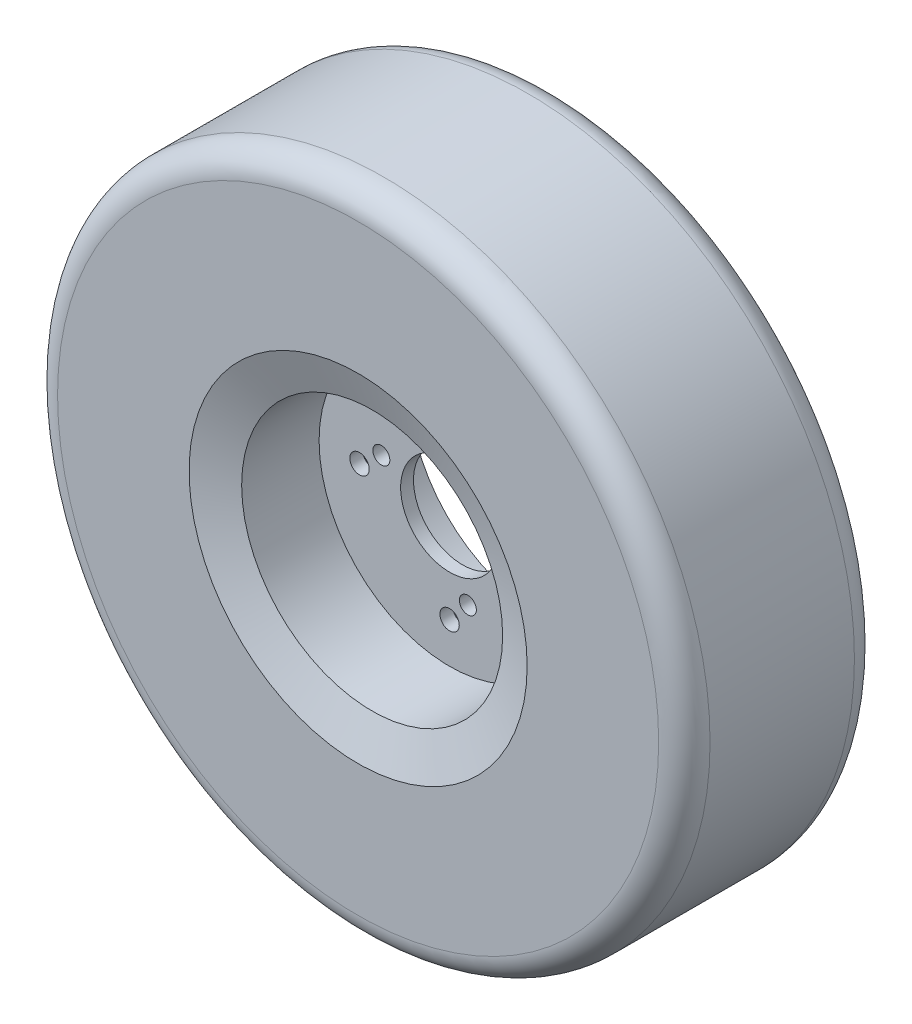
SolidWorks part; units mm, degrees
material "wheel"
ref_plane "Front Plane" through (0, 0, 0) normal (0, 0, 1) x (1, 0, 0)
ref_plane "Top Plane" through (0, 0, 0) normal (0, 1, 0) x (1, 0, 0)
ref_plane "Right Plane" through (0, 0, 0) normal (1, 0, 0) x (0, 0, -1)
sketch "Sketch1" plane through (0, 0, 0) normal (0, 0, 1) x (1, 0, 0)
  circle A0 centre (0, 0) radius 50.8
  circle A1 centre (0, 0) radius 127
  dimension "D1" = 254
  dimension "D2" = 101.6
extrude "Boss-Extrude1" add sketch "Sketch1" along normal mid plane 76.2
chamfer "Chamfer1" distance 15 angle 20 2 edges at (50.8, 0, 38.1) (50.8, 0, -38.1) first distance on face at (127, 0, 38.1) first distance on face at (127, 0, -38.1)
fillet "Fillet1" radius 10 2 edges at (127, 0, -38.1) (127, 0, 38.1)
sketch "Sketch2" plane through (0, 0, 0) normal (0, 0, 1) x (1, 0, 0)
  circle A0 centre (0, 0) radius 50.8
  circle A1 centre (0, 0) radius 50.8 construction
  circle A2 centre (0, 0) radius 19.05
  dimension "D1" = 38.1
extrude "Boss-Extrude2" add sketch "Sketch2" along normal mid plane 5
hole_wizard "19/64 (0.29688) Diameter Hole1" positions "Sketch3" profile "Sketch4" hole size "19/64" standard "ANSI Inch"
sketch "Sketch3" plane through (0, 0, 2.5) normal (0, 0, 1) x (1, 0, 0)
  line L0 (0, -35.052) -> (0, 0) construction
  line L1 (0, 0) -> (35.052, 0) construction
  line L3 (0, 35.052) -> (0, 0) construction
  line L4 (0, 0) -> (-35.052, 0) construction
  circle A0 centre (0, 0) radius 35.052 construction
  point P0 (0, 35.052)
  point P2 (35.052, 0)
  point P4 (0, -35.052)
  point P6 (-35.052, 0)
  dimension "D1" = 70.104
sketch "Sketch4" plane through (0, 35.052, 2.5) normal (1, 0, 0) x (0, -1, 0)
  line L0 (0, 0) -> (0, 21.0155)
  line L1 (0, 21.0155) -> (3.7704, 18.75)
  line L2 (3.7704, 18.75) -> (3.7704, 0)
  line L5 (3.7704, 0) -> (0, 0)
  line L10 (0, 21.0155) -> (-3.7704, 18.75) construction
  line L11 (0, -6.35) -> (0, 107.95) construction
  dimension "Hole Dia." = 7.5408
  dimension "Hole Depth" = 18.75
  dimension "Drill Angle" = 118
hole_wizard "M6 Clearance Hole1" positions "Sketch7" profile "Sketch8" hole size "M6" standard "ANSI Metric"
sketch "Sketch7" plane through (0, 0, 2.5) normal (0, 0, 1) x (1, 0, 0)
  line L0 (-26.563, 7.1175) -> (0, 0) construction
  line L1 (0, 0) -> (7.1175, -26.563) construction
  line L4 (0, 0) -> (19.4454, 19.4454) construction
  line L6 (-35.052, 0) -> (35.052, 0) construction
  line L8 (0, 0) -> (-19.4454, -19.4454) construction
  circle A0 centre (0, 0) radius 27.5 construction
  point P0 (-26.563, 7.1175)
  point P2 (19.4454, 19.4454)
  point P4 (7.1175, -26.563)
  dimension "D3" = 55
  dimension "D1" = 120
  dimension "D2" = 120
  dimension "D4" = 45
  dimension "D5" = 60
sketch "Sketch8" plane through (-26.563, 7.1175, 2.5) normal (1, 0, 0) x (0, -1, 0)
  line L0 (0, 0) -> (0, 20.7328)
  line L1 (0, 20.7328) -> (3.3, 18.75)
  line L2 (3.3, 18.75) -> (3.3, 0)
  line L5 (3.3, 0) -> (0, 0)
  line L10 (0, 20.7328) -> (-3.3, 18.75) construction
  line L11 (0, -6.35) -> (0, 107.95) construction
  dimension "Hole Dia." = 6.6
  dimension "Hole Depth" = 18.75
  dimension "Drill Angle" = 118
